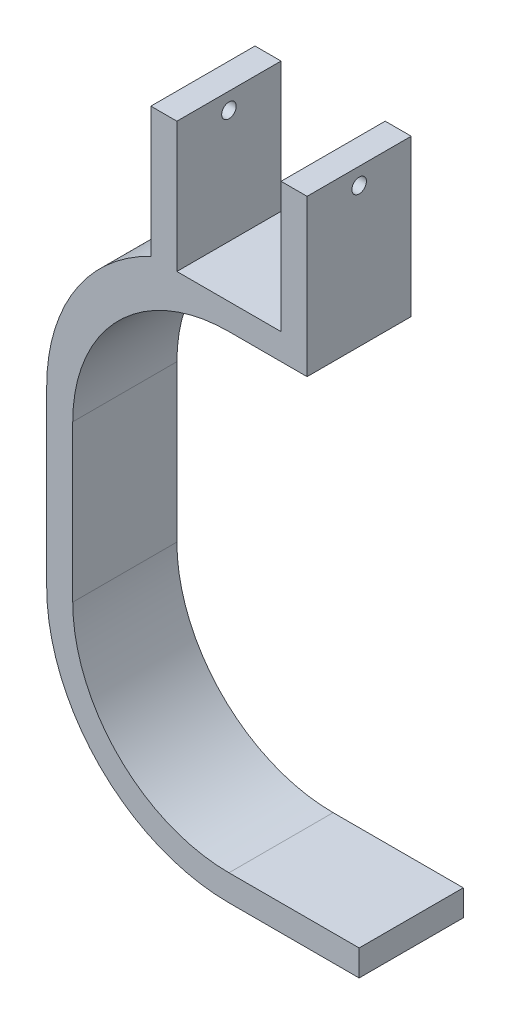
SolidWorks part; units mm, degrees
ref_plane "Front Plane" through (0, 0, 0) normal (0, 0, 1) x (1, 0, 0)
ref_plane "Top Plane" through (0, 0, 0) normal (0, 1, 0) x (1, 0, 0)
ref_plane "Right Plane" through (0, 0, 0) normal (1, 0, 0) x (0, 0, -1)
sketch "Sketch1" plane through (0, 0, 0) normal (0, 0, 1) x (1, 0, 0)
  line L0 (6.4485, 54.4648) -> (11.4485, 54.4648)
  line L1 (31.4485, 54.4648) -> (36.4485, 54.4648)
  line L2 (11.4485, 54.4648) -> (11.4485, 44.4648)
  line L3 (11.4485, 44.4648) -> (31.4485, 44.4648)
  line L4 (31.4485, 54.4648) -> (31.4485, 44.4648)
  line L6 (6.4485, 44.4648) -> (-13.5515, 44.4648)
  line L7 (6.4485, 39.4648) -> (36.4485, 39.4648)
  line L8 (6.4485, 44.4648) -> (6.4485, 54.4648)
  line L10 (36.4485, 39.4648) -> (36.4485, 54.4648)
  line L11 (6.4485, 39.4648) -> (-8.5515, 39.4648)
  line L12 (-13.5515, 44.4648) -> (-13.5515, 39.4648)
  line L13 (-13.5515, 44.4648) -> (-8.5515, 44.4648)
  line L14 (-13.5515, 44.4648) -> (-13.5515, -55.5352)
  line L15 (-13.5515, -55.5352) -> (-8.5515, -55.5352)
  line L16 (-8.5515, 39.4648) -> (-8.5515, -50.5352)
  line L17 (-13.5515, -55.5352) -> (46.4485, -55.5352)
  line L18 (-13.5515, -55.5352) -> (-13.5515, -50.5352)
  line L19 (-8.5515, -50.5352) -> (46.4485, -50.5352)
  line L20 (46.4485, -55.5352) -> (46.4485, -50.5352)
  point P0 (0, 22.3077)
  point P5 (0, 22.3077)
  dimension "D1" = 5
  dimension "D2" = 5
  dimension "D3" = 5
  dimension "D4" = 10
  dimension "D5" = 20
  dimension "D6" = 20
  dimension "D7" = 100
  dimension "D8" = 5
  dimension "D9" = 5
  dimension "D10" = 5
  dimension "D11" = 60
extrude "Boss-Extrude1" add sketch "Sketch1" along normal blind 20 contours L17 L20 L19 L16 L11 L7 L10 L1 L4 L3 L2 L0 L8 L6 L12 L14 L15 region at (8.9485, 53.2118, 0)
fillet "Fillet1" radius 30 2 edges at (-8.5515, -50.5352, 10) (-8.5515, 39.4648, 10)
fillet "Fillet2" radius 35 2 edges at (-13.5515, -55.5352, 10) (-13.5515, 44.4648, 10)
sketch "Sketch2" plane through (0, 54.4648, 0) normal (0, 1, 0) x (1, 0, 0)
  line L1 (6.4485, 0) -> (11.4485, 0)
  line L2 (6.4485, 0) -> (6.4485, -20)
  line L3 (6.4485, -20) -> (11.4485, -20)
  line L4 (11.4485, 0) -> (11.4485, -20)
  line L5 (36.4485, 0) -> (31.4485, 0)
  line L6 (36.4485, 0) -> (36.4485, -20)
  line L7 (36.4485, -20) -> (31.4485, -20)
  line L8 (31.4485, 0) -> (31.4485, -20)
extrude "Boss-Extrude2" add sketch "Sketch2" along normal blind 15
sketch "Sketch3" plane through (36.4485, 0, 0) normal (1, 0, 0) x (0, 0, -1)
  line L0 (-20, 44.4648) -> (0, 44.4648) construction
  circle A0 centre (-10, 66.2648) radius 1.4
  dimension "D1" = 2.8
  dimension "D2" = 21.8
extrude "Cut-Extrude1" cut sketch "Sketch3" against normal blind 45
